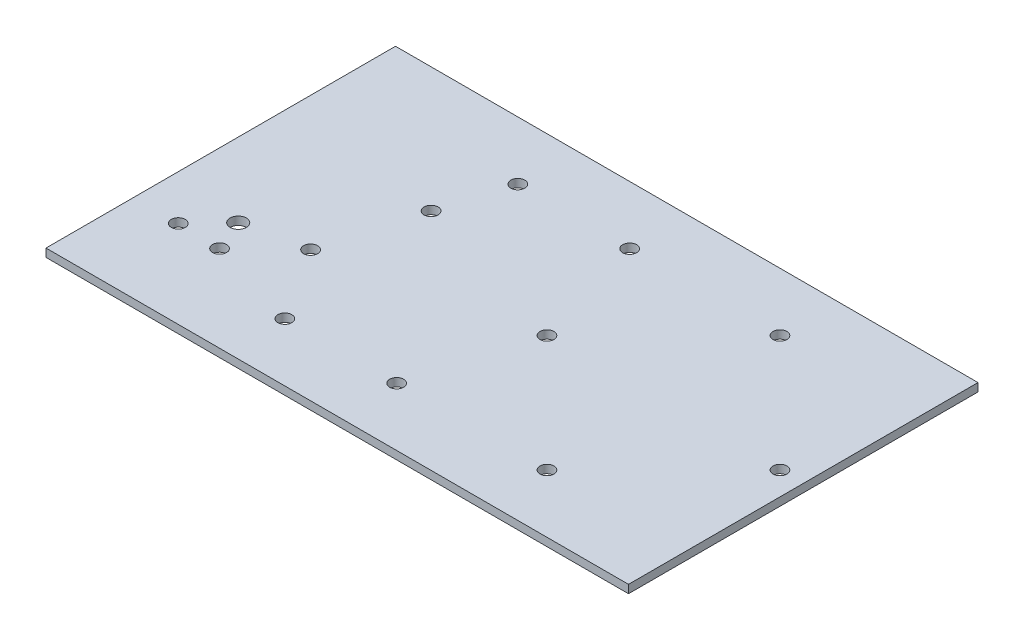
SolidWorks part; units mm, degrees
ref_plane "前基準面" through (0, 0, 0) normal (0, 0, 1) x (1, 0, 0)
ref_plane "上基準面" through (0, 0, 0) normal (0, 1, 0) x (1, 0, 0)
ref_plane "右基準面" through (0, 0, 0) normal (1, 0, 0) x (0, 0, -1)
sketch "草圖1" plane through (0, 0, 0) normal (0, 1, 0) x (1, 0, 0)
  line L0 (0, 0) -> (0, 112.1795) construction
  line L1 (-190, 75) -> (60, 75)
  line L2 (-190, 75) -> (-190, -75)
  line L3 (-190, -75) -> (60, -75)
  line L4 (60, 75) -> (60, -75)
  line L5 (0, 0) -> (222.1154, 0) construction
  line L6 (0, 0) -> (0, -82.367) construction
  line L7 (0, 0) -> (-107.6818, 0) construction
  circle A0 centre (0, 0) radius 50 construction
  circle A1 centre (0, 50) radius 3
  circle A2 centre (50, 0) radius 3
  circle A3 centre (-50, 0) radius 3
  circle A4 centre (0, -50) radius 3
  dimension "D4" = 100
  dimension "D5" = 6
  dimension "D6" = 6
  dimension "D7" = 6
  dimension "D8" = 6
  dimension "D1" = 250
  dimension "D2" = 60
  dimension "D3" = 150
extrude "填料-伸長1" add sketch "草圖1" against normal blind 5 contours L3 L4 L1 L2
extrude "除料-伸長1" cut sketch "草圖1<4>" against normal blind 5 contours A1
sketch "草圖1<4>" plane through (0, 0, 0) normal (0, 1, 0) x (1, 0, 0) same geometry as "草圖1"
extrude "除料-伸長2" cut sketch "草圖1<5>" against normal blind 5 contours A3
sketch "草圖1<5>" plane through (0, 0, 0) normal (0, 1, 0) x (1, 0, 0) same geometry as "草圖1"
extrude "除料-伸長3" cut sketch "草圖1<6>" against normal blind 5 contours A4
sketch "草圖1<6>" plane through (0, 0, 0) normal (0, 1, 0) x (1, 0, 0) same geometry as "草圖1"
extrude "除料-伸長4" cut sketch "草圖1<7>" against normal blind 5 contours A2
sketch "草圖1<7>" plane through (0, 0, 0) normal (0, 1, 0) x (1, 0, 0) same geometry as "草圖1"
sketch "草圖2" plane through (0, 0, 0) normal (0, 1, 0) x (1, 0, 0)
  line L0 (-190, -75) -> (60, -75) construction
  line L1 (-190, 75) -> (-190, -75) construction
  circle A0 centre (-170.76, -37.46) radius 3
  dimension "D1" = 6
  dimension "D2" = 37.54
  dimension "D3" = 19.24
extrude "除料-伸長5" cut sketch "草圖2" against normal blind 5
sketch "草圖3" plane through (0, 0, 0) normal (0, 1, 0) x (1, 0, 0)
  line L0 (-190, 75) -> (-190, -75) construction
  line L1 (-190, -75) -> (60, -75) construction
  circle A0 centre (-158.16, -24.34) radius 3.5
  circle A1 centre (-152.57, -37.93) radius 3
  dimension "D1" = 7
  dimension "D2" = 6
  dimension "D3" = 37.43
  dimension "D4" = 37.07
  dimension "D5" = 31.84
  dimension "D6" = 50.66
extrude "除料-伸長6" cut sketch "草圖3" against normal blind 45 contours A1
extrude "除料-伸長7" cut sketch "草圖3<3>" against normal blind 45 contours A0
sketch "草圖3<3>" plane through (0, 0, 0) normal (0, 1, 0) x (1, 0, 0) same geometry as "草圖3"
sketch "草圖4" plane through (0, 0, 0) normal (0, 1, 0) x (1, 0, 0)
  circle A0 centre (-64.5, -50) radius 3
  circle A1 centre (-112.5, -50) radius 3
  circle A2 centre (0, -50) radius 3 construction
  circle A3 centre (0, -50) radius 3
  dimension "D1" = 6
  dimension "D2" = 6
  dimension "D3" = 64.5
  dimension "D4" = 48
extrude "除料-伸長8" cut sketch "草圖4" against normal blind 5 contours A1
extrude "除料-伸長9" cut sketch "草圖4<3>" against normal blind 5 contours A0
sketch "草圖4<3>" plane through (0, 0, 0) normal (0, 1, 0) x (1, 0, 0) same geometry as "草圖4"
sketch "草圖5" plane through (0, 0, 0) normal (0, 1, 0) x (1, 0, 0)
  line L0 (-190, 75) -> (-190, -75) construction
  line L2 (-190, -75) -> (60, -75) construction
  circle A0 centre (-132.61, -18.84) radius 3
  circle A1 centre (-121.14, 21.42) radius 3
  dimension "D1" = 6
  dimension "D2" = 6
  dimension "D3" = 57.39
  dimension "D4" = 56.16
  dimension "D5" = 11.47
  dimension "D6" = 40.26
extrude "除料-伸長10" cut sketch "草圖5" against normal blind 5
sketch "草圖6" plane through (0, 0, 0) normal (0, 1, 0) x (1, 0, 0)
  line L4 (-190, 75) -> (-190, -75)
  line L5 (-190, -75) -> (60, -75)
  line L6 (60, -75) -> (60, 75)
  line L7 (60, 75) -> (-190, 75)
  line L8 (-190, 75) -> (-190, -75)
  line L9 (-190, -75) -> (60, -75)
  line L10 (60, -75) -> (60, 75)
  line L11 (60, 75) -> (-190, 75)
  circle A0 centre (-170.76, -37.46) radius 3 construction
  circle A1 centre (-158.16, -24.34) radius 3.5 construction
  circle A2 centre (-152.57, -37.93) radius 3 construction
  circle A3 centre (-132.61, -18.84) radius 3 construction
  circle A4 centre (-112.5, -50) radius 3 construction
  circle A5 centre (-121.14, 21.42) radius 3 construction
  circle A6 centre (-50, 0) radius 3 construction
  circle A7 centre (-64.5, -50) radius 3 construction
  circle A8 centre (0, 50) radius 3 construction
  circle A9 centre (0, -50) radius 3 construction
  circle A10 centre (50, 0) radius 3 construction
  circle A11 centre (-170.76, -37.46) radius 3
  circle A12 centre (-158.16, -24.34) radius 3.5
  circle A13 centre (-152.57, -37.93) radius 3
  circle A14 centre (-132.61, -18.84) radius 3
  circle A15 centre (-112.5, -50) radius 3
  circle A16 centre (-121.14, 21.42) radius 3
  circle A17 centre (-50, 0) radius 3
  circle A18 centre (-64.5, -50) radius 3
  circle A19 centre (0, 50) radius 3
  circle A20 centre (0, -50) radius 3
  circle A21 centre (50, 0) radius 3
  dimension "D1" = 0
extrude "除料-伸長11" cut sketch "草圖6" against normal blind 1.5
sketch "草圖7" plane through (0, -1.5, 0) normal (0, 1, 0) x (1, 0, 0)
  line L0 (0, 50) -> (-157.2363, 50) construction
  circle A0 centre (-64.5, 50) radius 3
  circle A1 centre (-112.5, 50) radius 3
  circle A2 centre (-64.5, -50) radius 3 construction
  circle A3 centre (-112.5, -50) radius 3 construction
  circle A4 centre (-64.5, -50) radius 3
  circle A5 centre (-112.5, -50) radius 3
  dimension "D1" = 64.5
  dimension "D3" = 6
  dimension "D4" = 6
  dimension "D2" = 48
extrude "除料-伸長12" cut sketch "草圖7" against normal through all
